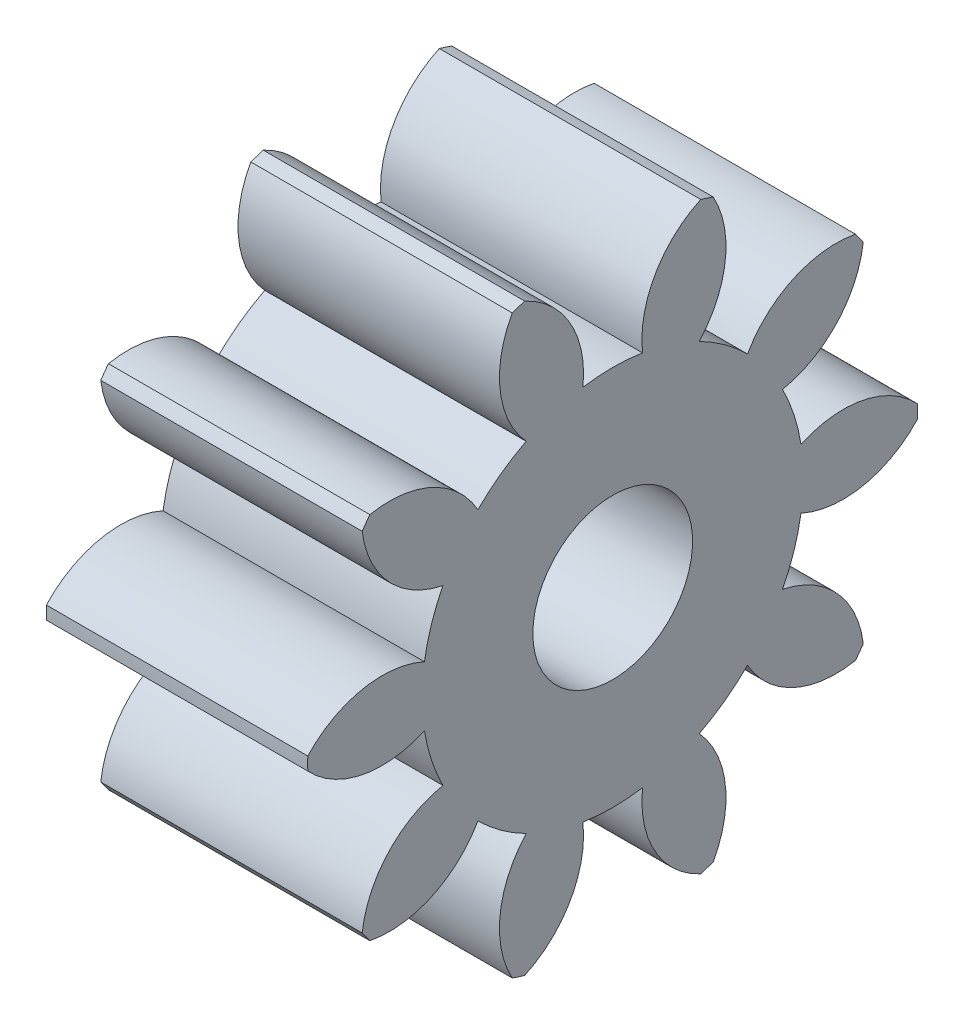
SolidWorks part; units mm, degrees
ref_plane "Plane1" through (0, 0, 0) normal (0, 0, 1) x (1, 0, 0)
ref_plane "Plane2" through (0, 0, 0) normal (0, 1, 0) x (1, 0, 0)
ref_plane "Plane3" through (0, 0, 0) normal (1, 0, 0) x (0, 0, -1)
other "Configuration Table"
sketch "HoldingSke" plane through (0, 0, 0) normal (0, 1, 0) x (1, 0, 0)
  line L0 (0, 0) -> (0.2814, -0.0496)
  line L1 (-15, 0) -> (100, 0) construction
  line L2 (0, 0) -> (-2.1039, 2.3779)
  line L3 (0, 0) -> (-11.863, 4.5341)
  line L4 (0, 0) -> (8.5048, 1.4996)
  line L5 (0, 0) -> (-46.8476, -17.4728)
  line L6 (0, 0) -> (-14.9213, -10.0675)
  line L7 (-2.1039, 2.3779) -> (8.6586, 51.2059)
  line L8 (-76.2, 54.61) -> (-74.4, 54.61)
  line L9 (-71.009, 38.7566) -> (-53.1078, 45.2721)
  line L10 (-76.2, 71.12) -> (104.1128, 71.12)
  line L11 (0, 0) -> (-18, 0)
  line L12 (-76.2, 101.6) -> (-76.083, 101.6)
  line L13 (24.9733, 27.94) -> (52.9518, 28.4284)
  line L14 (24.9733, 27.94) -> (24.9743, 27.94)
  line L15 (24.9733, 27.94) -> (100.4006, 29.5858)
  line L16 (-63.627, -3.5) -> (-12.827, -3.5)
  circle A0 centre (0, 0) radius 5.5
  circle A1 centre (0, 0) radius 13.124
  circle A2 centre (0, 0) radius 37.5
  circle A3 centre (0, 0) radius 5.5
  dimension "Num_teeth" = 10
  dimension "Pitch_radius" = 180.3128
  dimension "Width" = 18
  dimension "Thickness" = 18
sketch "BasProSke" plane through (0, 0, 0) normal (0, 1, 0) x (1, 0, 0)
  line L0 (-10, 0) -> (60, 0) construction
  line L1 (0, 0) -> (0, 21)
  line L2 (0, 0) -> (18, 0)
  line L3 (18, 0) -> (18, 21)
  line L4 (18, 21) -> (0, 21)
  dimension "Thickness" = 18
  dimension "Diameter" = 42
revolve "Base-Revolve" add sketch "BasProSke" angle 360 about L0
sketch "TooCutSke" plane through (0, 0, 0) normal (1, 0, 0) x (0, 0, -1)
  line L1 (0, 0) -> (0, 107) construction
  line L2 (0, 0) -> (-2.942, 17.2509) construction
  line L3 (0, 0) -> (-10.7017, 32.9365) construction
  line L4 (-2.942, 17.2509) -> (-5.3509, 16.4682) construction
  arc A0 (2.0535, 12.9624) -> (-2.0535, 12.9624) centre (0, 0) ccw
  arc A1 (6.0946, 20.1227) -> (-6.0946, 20.1227) centre (0, 0) ccw
  circle A2 centre (0, 0) radius 17.5 construction
  circle A3 centre (0, 0) radius 16.4446 construction
  arc A4 (-2.0535, 12.9624) -> (-6.0946, 20.1227) centre (-9.0081, 13.7579) ccw
  arc A5 (6.0946, 20.1227) -> (2.0535, 12.9624) centre (9.0081, 13.7579) ccw
extrude "ToothCut" cut sketch "TooCutSke" along normal through all
fillet "Breaks" [suppressed] radius 0.07 tangent propagation no
fillet "RootFillets" [suppressed] radius 0.876
pattern_circular "TeethCuts" count 10 every 36 about axis through (-10, 0, 0) along (1, 0, 0) of "ToothCut", "RootFillets", "Breaks"
sketch "HubNeaOneSke" plane through (0, 0, 0) normal (-1, 0, 0) x (0, 0, 1)
  circle A0 centre (0, 0) radius 13.124
  dimension "Diameter" = 26.248
extrude "HubNearOne" [suppressed] add sketch "HubNeaOneSke" along normal blind 32.0001
sketch "HubNeaBotSke" plane through (0, 0, 0) normal (-1, 0, 0) x (0, 0, 1)
  circle A0 centre (0, 0) radius 13.124
  dimension "Diameter" = 26.248
extrude "HubNearBoth" [suppressed] add sketch "HubNeaBotSke" along normal blind 16
ref_plane "FarPln" through (18, 0, 0) normal (1, 0, 0) x (0, 0, -1)
sketch "HubFarSke" plane through (18, 0, 0) normal (1, 0, 0) x (0, 0, -1)
  circle A0 centre (0, 0) radius 13.124
  dimension "Diameter" = 26.248
extrude "HubFar" [suppressed] add sketch "HubFarSke" along normal blind 16
sketch "BorSke" plane through (0, 0, 0) normal (1, 0, 0) x (0, 0, -1)
  circle A0 centre (0, 0) radius 5.5
  dimension "Diameter" = 11
extrude "Bore" cut sketch "BorSke" along normal mid plane 100.0001
sketch "KeySke" plane through (0, 0, 0) normal (1, 0, 0) x (0, 0, -1)
  line L0 (-2, 0) -> (-2, 7.3)
  line L1 (-2, 7.3) -> (2, 7.3)
  line L2 (2, 7.3) -> (2, 0)
  line L3 (0, 0) -> (0, 34) construction
  line L4 (-2, 0) -> (2, 0)
  dimension "Width" = 4
extrude "Keyway" [suppressed] cut sketch "KeySke" along normal mid plane 100.0001
pattern_circular "Keyway2" [suppressed] count 2 every 90 about axis through (-10, 0, 0) along (1, 0, 0)
equation "' \"Module@HoldingSke\" = 6.35"
equation "' \"Num_teeth@HoldingSke\" = 12"
equation "' \"Ap@HoldingSke\" =  20"
equation "' \"Ap@HoldingSke\" = 20"
equation "' \"Width@HoldingSke\" = 0.5 * 25.4"
equation "' \"Hub_dia@HoldingSke\"= 1 * 25.4"
equation "' \"Hub_dia@HoldingSke\" = 1 * 25.4"
equation "' \"Overall_len@HoldingSke\" = 1.0 * 25.4"
equation "' \"Bore@HoldingSke\" = 0.75 * 25.4"
equation "' \"T_dim@HoldingSke\" = 0.1 * 25.4"
equation "' \"Width@KeySke\" = 0.25 * 25.4"
equation "' \"Show_teeth@HoldingSke\" = 13"
equation "' \"Backlash@HoldingSke\" = 0.009 * 25.4"
equation "' \"Addendum_fac@HoldingSke\" = 1.0"
equation "' \"Dedendum_fac@HoldingSke\" = 1.25"
equation "' \"Dedendum_add@HoldingSke\" = 0.00005 * 25.4"
equation "' \"Clearance_fac@HoldingSke\" = 0.25"
equation "\"Pitch@HoldingSke\" = 1 / \"Module@HoldingSke\""
equation "\"Overcut_dia@TooCutSke\" = (\"Num_teeth@HoldingSke\" + 2 * \"Addendum_fac@HoldingSke\") / \"Pitch@HoldingSke\" + 0.002 * 25.4"
equation "\"Pitch_dia@TooCutSke\" = \"Num_teeth@HoldingSke\" / \"Pitch@HoldingSke\""
equation "\"Base_dia@TooCutSke\" = \"Num_teeth@HoldingSke\" / \"Pitch@HoldingSke\" * cos((\"Ap@HoldingSke\"  * 3.14159265 / 180))"
equation "\"Root_dia@TooCutSke\" = (\"Num_teeth@HoldingSke\" + 2) / \"Pitch@HoldingSke\" - 2 * (\"Addendum_fac@HoldingSke\" + \"Dedendum_fac@HoldingSke\") / \"Pitch@HoldingSke\" - \"Dedendum_add@HoldingSke\" * 2"
equation "\"Half_ang@TooCutSke\" = 180 / \"Num_teeth@HoldingSke\""
equation "\"Half_CT@TooCutSke\" = \"Num_teeth@HoldingSke\" / \"Pitch@HoldingSke\" * sin((3.14159265 / 2 / \"Num_teeth@HoldingSke\")) / 2 - 7 * \"Backlash@HoldingSke\" / 4"
equation "\"Flank_rad@TooCutSke\" = \"Num_teeth@HoldingSke\" / \"Pitch@HoldingSke\" / 5"
equation "\"Radius@RootFillets\" = \"Clearance_fac@HoldingSke\" / \"Pitch@HoldingSke\" + \"Dedendum_add@HoldingSke\""
equation "\"Break_rad@Breaks\" = 0.02 / \"Pitch@HoldingSke\""
equation "\"Thickness@HoldingSke\" = \"Width@HoldingSke\""
equation "\"OAL@HoldingSke\" = \"Thickness@HoldingSke\""
equation "\"MHD@HoldingSke\" = (\"Num_teeth@HoldingSke\" + 2) / \"Pitch@HoldingSke\" - 2 * (\"Addendum_fac@HoldingSke\" + \"Dedendum_fac@HoldingSke\")  / \"Pitch@HoldingSke\" - \"Dedendum_add@HoldingSke\" * 2"
equation "\"MBD@HoldingSke\" = (\"Num_teeth@HoldingSke\" + 2) / \"Pitch@HoldingSke\" - 2 * (\"Addendum_fac@HoldingSke\" + \"Dedendum_fac@HoldingSke\")  / \"Pitch@HoldingSke\" - \"Dedendum_add@HoldingSke\" * 2 - 0.002 * 25.4"
equation "\"MHD@HoldingSke\" = ((sgn( \"MHD@HoldingSke\" - \"Hub_dia@HoldingSke\" )-1)*( \"MHD@HoldingSke\" - \"Hub_dia@HoldingSke\" ))/-2+ \"Hub_dia@HoldingSke\""
equation "\"MBD@HoldingSke\" = ((sgn( \"MBD@HoldingSke\" - \"Bore@HoldingSke\" )-1)*( \"MBD@HoldingSke\" - \"Bore@HoldingSke\" ))/-2+ \"Bore@HoldingSke\""
equation "\"OAL@HoldingSke\" = ((sgn( \"OAL@HoldingSke\" - \"Overall_len@HoldingSke\" )+1)*( \"OAL@HoldingSke\" - \"Overall_len@HoldingSke\" ))/2 + \"Overall_len@HoldingSke\" + 0.000002 * 25.4"
equation "\"Num_teeth@TeethCuts\" = int( \"Show_teeth@HoldingSke\" ) + 1"
equation "\"Num_teeth@TeethCuts\" = ((sgn( \"Num_teeth@TeethCuts\" - \"Num_teeth@HoldingSke\" )-1)*( \"Num_teeth@TeethCuts\" - \"Num_teeth@HoldingSke\" ))/-2+ \"Num_teeth@HoldingSke\""
equation "\"Num_teeth@TeethCuts\" = ((sgn( \"Num_teeth@TeethCuts\" - 2.0)+1)*( \"Num_teeth@TeethCuts\" - 2.0))/2 +2.0"
equation "\"Angle@TeethCuts\" = 360.0 / \"Num_teeth@HoldingSke\""
equation "\"Diameter@BasProSke\" = (\"Num_teeth@HoldingSke\" + 2 * \"Addendum_fac@HoldingSke\") / \"Pitch@HoldingSke\""
equation "\"Thickness@BasProSke\"  = \"Thickness@HoldingSke\""
equation "' \"Fillet_rad@BasProSke\" =  \"Thickness@HoldingSke\" * 0.05"
equation "' \"Fillet_rad@BasProSke\" = \"Thickness@HoldingSke\" * 0.05"
equation "\"MHD@HoldingSke\" = ((sgn( \"MHD@HoldingSke\" - \"Root_dia@TooCutSke\" )-1)*( \"MHD@HoldingSke\" - \"Root_dia@TooCutSke\" ))/-2+ \"Root_dia@TooCutSke\""
equation "\"Diameter@HubNeaOneSke\" = \"MHD@HoldingSke\""
equation "\"Length@HubNearOne\" = \"OAL@HoldingSke\" - \"Thickness@BasProSke\""
equation "\"Diameter@HubNeaBotSke\" = \"MHD@HoldingSke\""
equation "\"Length@HubNearBoth\" = ( \"OAL@HoldingSke\" - \"Thickness@BasProSke\" ) / 2.0"
equation "\"Thickness@FarPln\" = \"Thickness@BasProSke\""
equation "\"Diameter@HubFarSke\" = \"MHD@HoldingSke\""
equation "\"Length@HubFar\" = ( \"OAL@HoldingSke\" - \"Thickness@BasProSke\" ) / 2.0"
equation "\"Diameter@BorSke\" = \"MBD@HoldingSke\""
equation "\"D1@Bore\" = \"OAL@HoldingSke\" * 2.0"
equation "\"D1@Keyway\" = \"OAL@HoldingSke\" * 2.0"
equation "\"Offset@KeySke\" = \"T_dim@HoldingSke\" + \"MBD@HoldingSke\" / 2.0"
